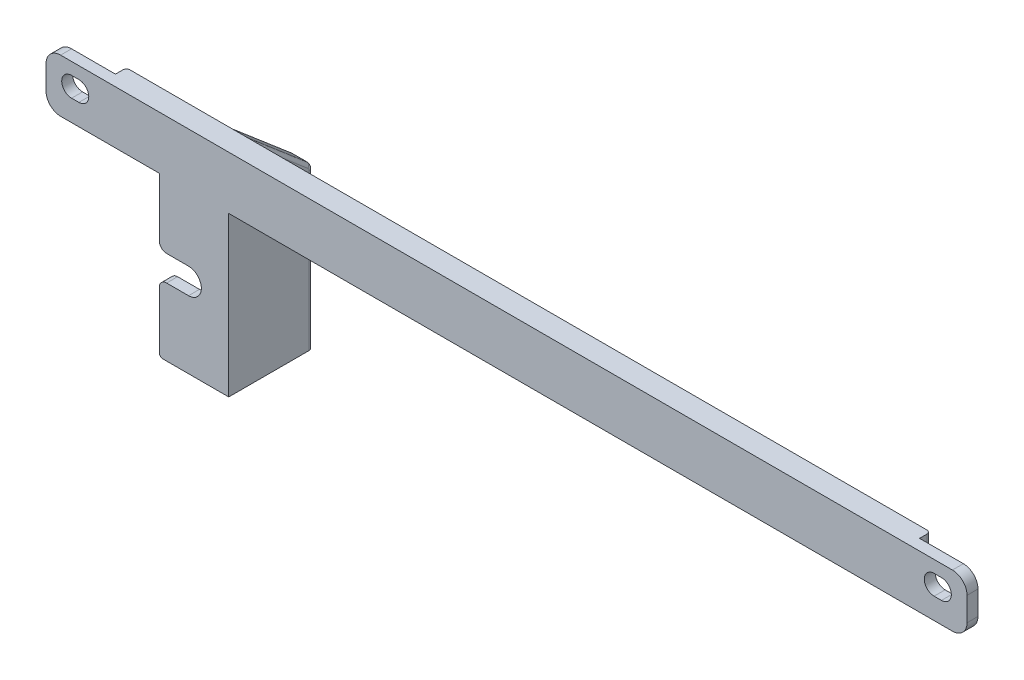
SolidWorks part; units mm, degrees
ref_plane "Front Plane" through (0, 0, 0) normal (0, 0, 1) x (1, 0, 0)
ref_plane "Top Plane" through (0, 0, 0) normal (0, 1, 0) x (1, 0, 0)
ref_plane "Right Plane" through (0, 0, 0) normal (1, 0, 0) x (0, 0, -1)
sketch "Sketch1" plane through (0, 0, 0) normal (0, 0, 1) x (1, 0, 0)
  line L0 (0, 0) -> (0, 14.5)
  line L1 (0, 14.5) -> (252, 14.5)
  line L3 (50, -43.5) -> (31, -43.5)
  line L4 (31, -43.5) -> (31, 0)
  line L5 (31, 0) -> (0, 0)
  line L6 (252, 14.5) -> (252, 0)
  line L7 (252, 0) -> (50, 0)
  line L8 (50, 0) -> (50, -43.5)
  line L9 (245, 8.5) -> (243, 8.5) construction
  line L10 (245, 5.8) -> (243, 5.8)
  line L11 (245, 11.2) -> (243, 11.2)
  line L12 (7, 8.5) -> (9, 8.5) construction
  line L13 (7, 11.2) -> (9, 11.2)
  line L14 (7, 5.8) -> (9, 5.8)
  arc A1 (245, 5.8) -> (245, 11.2) centre (245, 8.5) ccw
  arc A2 (243, 11.2) -> (243, 5.8) centre (243, 8.5) ccw
  arc A3 (7, 11.2) -> (7, 5.8) centre (7, 8.5) ccw
  arc A4 (9, 5.8) -> (9, 11.2) centre (9, 8.5) ccw
  point P13 (244, 8.5)
  point P18 (8, 8.5)
  dimension "D7" = 2.7
  dimension "D12" = 2.7
  dimension "D1" = 14.5
  dimension "D2" = 31
  dimension "D3" = 43.5
  dimension "D4" = 19
  dimension "D5" = 252
  dimension "D6" = 2
  dimension "D8" = 7
  dimension "D9" = 7
  dimension "D10" = 2
  dimension "D11" = 6
extrude "Boss-Extrude1" add sketch "Sketch1" against normal blind 3
sketch "Sketch6" plane through (0, 0, -3) normal (0, 0, -1) x (-1, 0, 0)
  line L7 (-31, -43.5) -> (-31, -37.5)
  line L12 (-31, 0) -> (-31, -43.5) construction
  line L13 (-31, -37.5) -> (-44, -37.5)
  line L14 (-44, -37.5) -> (-44, 0)
  line L15 (-44, 0) -> (-50, 0)
  line L16 (-50, 0) -> (-50, -43.5)
  line L17 (-50, -43.5) -> (-31, -43.5)
  dimension "D1" = 6
  dimension "D2" = 6
extrude "Boss-Extrude2" add sketch "Sketch6" along normal blind 20
sketch "Sketch7" plane through (0, 0, -3) normal (0, 0, -1) x (-1, 0, 0)
  line L0 (-252, 14.5) -> (0, 14.5) construction
  line L1 (-236, 14.5) -> (-16, 14.5)
  line L2 (-236, 14.5) -> (-236, 0)
  line L3 (-236, 0) -> (-16, 0)
  line L4 (-16, 14.5) -> (-16, 0)
  line L5 (0, 0) -> (-31, 0) construction
  line L6 (0, 14.5) -> (0, 0) construction
  line L7 (-252, 0) -> (-252, 14.5) construction
  dimension "D1" = 16
  dimension "D2" = 16
extrude "Boss-Extrude3" add sketch "Sketch7" along normal blind 3
sketch "Sketch8" plane through (44, 0, 0) normal (-1, 0, 0) x (0, 0, 1)
  line L0 (-23, 0) -> (-6, 14.5)
  line L1 (-6, 14.5) -> (-6, 0)
  line L2 (-6, 0) -> (-23, 0)
extrude "Boss-Extrude4" add sketch "Sketch8" against normal blind 6
sketch "Sketch3" plane through (0, 0, 0) normal (0, 0, 1) x (1, 0, 0)
  line L1 (39, -18) -> (31, -18)
  line L6 (31, 0) -> (31, -43.5) construction
  line L7 (31, -18) -> (31, -25)
  line L8 (31, -25) -> (39, -25)
  line L9 (31, -43.5) -> (50, -43.5) construction
  arc A1 (39, -25) -> (39, -18) centre (39, -21.5) ccw
  point P0 (0, 0)
  dimension "D1" = 8
  dimension "D4" = 7
  dimension "D5" = 22
extrude "Cut-Extrude1" cut sketch "Sketch3" against normal through all
fillet "Fillet1" radius 4 4 edges at (0, 0, -1.5) (0, 14.5, -1.5) (252, 0, -1.5) (252, 14.5, -1.5)
fillet "Fillet2" radius 2 3 edges at (47, 0, -23) (31, -18, -1.5) (31, -25, -1.5)
fillet "Fillet3" radius 1 15 edges at (44, 7.5494, -14.1489) (44, -0.0849, -22.816) (50, 7.5494, -14.1489) (50, -0.0849, -22.816) (37.5, 0, -3) (44, -37.5, -13) (31, -37.5, -13) (31, -43.5, -11.5) (37.5, -37.5, -23) (40.5, -43.5, -23) (31, -40.5, -23) (44, -19.2114, -23) (50, -22.2114, -23) (236, 7.25, -6) (16, 7.25, -6)
